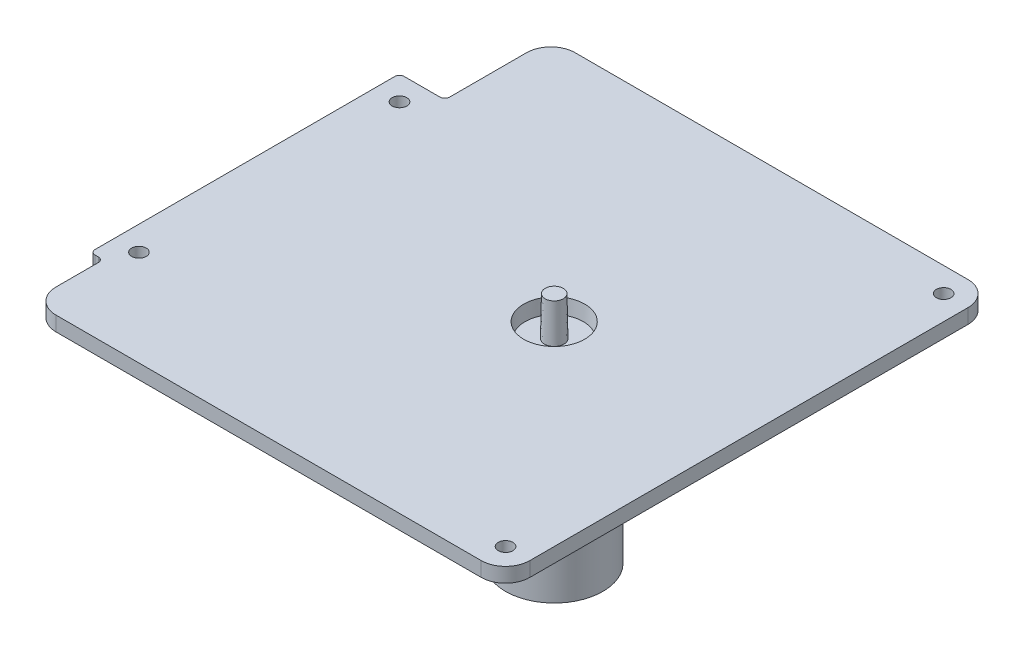
SolidWorks part; units mm, degrees
ref_plane "Front Plane" through (0, 0, 0) normal (0, 0, 1) x (1, 0, 0)
ref_plane "Top Plane" through (0, 0, 0) normal (0, 1, 0) x (1, 0, 0)
ref_plane "Right Plane" through (0, 0, 0) normal (1, 0, 0) x (0, 0, -1)
ref_plane "Plane1" through (0, 23, 0) normal (0, 1, 0) x (1, 0, 0)
sketch "Sketch1" plane through (0, 23, 0) normal (0, 1, 0) x (1, 0, 0)
  line L0 (98.3054, 50) -> (98.3054, 28.2195)
  line L1 (189, 50) -> (98.3054, 50)
  line L2 (189, 50) -> (189, -50)
  line L3 (189, -50) -> (97.6502, -50)
  line L5 (98.3054, 28.2195) -> (89, 28.2195)
  line L6 (89, 28.2195) -> (89, -35.308)
  line L7 (89, -35.308) -> (91.6598, -35.308)
  line L8 (91.6598, -35.308) -> (91.6598, -50)
  line L9 (91.6598, -50) -> (97.6502, -50)
  line L10 (94.8054, 33.2195) -> (98.3054, 33.2195) construction
  line L11 (184, 45) -> (184, 50) construction
  line L12 (93.3054, 31.7195) -> (93.3054, 28.2195) construction
  line L13 (99.4745, -35.308) -> (86.1225, -35.308) construction
  line L14 (88.1598, -40.308) -> (91.6598, -40.308) construction
  line L15 (86.6598, -38.808) -> (86.6598, -35.308) construction
  line L16 (189, 0) -> (190, 0) construction
  line L17 (190, -60) -> (190, 60) construction
  line L18 (105.0183, -40) -> (185.0183, -40) construction
  line L19 (105.0183, -40) -> (105.0183, 40) construction
  line L20 (105.0183, 40) -> (185.0183, 40) construction
  line L21 (185.0183, -40) -> (185.0183, 40) construction
  line L22 (184, 45) -> (189, 45) construction
  line L23 (184, -45) -> (189, -45) construction
  line L24 (184, -45) -> (184, -50) construction
  line L25 (94, 23.2195) -> (94, 28.2195) construction
  line L26 (94, 23.2195) -> (89, 23.2195) construction
  line L27 (94, -30.308) -> (94, -35.308) construction
  line L28 (94, -30.308) -> (89, -30.308) construction
  line L29 (190, -55) -> (190, 55) construction
  circle A0 centre (86.6598, -40.308) radius 1.5 construction
  circle A1 centre (93.3054, 33.2195) radius 1.5 construction
  circle A2 centre (184, 45) radius 1.5 construction
  circle A3 centre (184, 45) radius 1.5 construction
  circle A4 centre (184, -45) radius 1.5 construction
  circle A6 centre (94, 23.2195) radius 1.5 construction
  circle A7 centre (94, -30.308) radius 1.5 construction
  point P32 (185.0183, 0)
  dimension "D1" = 100
  dimension "D2" = 80
  dimension "D3" = 3.5
  dimension "D4" = 5
  dimension "D5" = 1
  dimension "D6" = 100
extrude "Boss-Extrude1" add sketch "Sketch1" along normal blind 3
fillet "Fillet3" radius 5 4 edges at (189, 24.5, -50) (98.3054, 24.5, -50) (91.6598, 24.5, 50) (189, 24.5, 50)
fillet "Fillet2" radius 1 4 edges at (89, 24.5, -28.2195) (98.3054, 24.5, -28.2195) (91.6598, 24.5, 35.308) (89, 24.5, 35.308)
sketch "Sketch2" plane through (0, 23, 0) normal (0, 1, 0) x (1, 0, 0)
  circle A0 centre (184, -45) radius 1.5 construction
  circle A1 centre (184, -45) radius 1.5
  circle A2 centre (94, -30.308) radius 1.5 construction
  circle A3 centre (94, -30.308) radius 1.5
  circle A4 centre (94, 23.2195) radius 1.5 construction
  circle A5 centre (94, 23.2195) radius 1.5
  circle A6 centre (184, 45) radius 1.5 construction
  circle A7 centre (184, 45) radius 1.5
extrude "Cut-Extrude1" cut sketch "Sketch2" along normal up to surface (3 mm away) up to face at (116.9913, 26, 1.7721)
sketch "Sketch5" plane through (0, 23, 0) normal (0, 1, 0) x (1, 0, 0)
  line L0 (189, 50) -> (189, -50) construction
  circle A0 centre (149, 0) radius 10
  circle A1 centre (149, 0) radius 6 construction
  circle A2 centre (149, 0) radius 2 construction
  point P4 (189, 0)
  dimension "D2" = 20
  dimension "D3" = 12
  dimension "D4" = 4
  dimension "D1" = 40
extrude "Boss-Extrude2" add sketch "Sketch5" against normal blind 40
sketch "Sketch3" plane through (0, 23, 0) normal (0, 1, 0) x (1, 0, 0)
  line L0 (189, 50) -> (189, -50) construction
  circle A0 centre (149, 0) radius 6
  circle A1 centre (149, 0) radius 6 construction
  point P6 (189, 0)
extrude "Cut-Extrude3" cut sketch "Sketch3" along normal blind 3 draft 5 draft outward yes
sketch "Sketch6" plane through (0, 23, 0) normal (0, 1, 0) x (1, 0, 0)
  circle A0 centre (149, 0) radius 2
  circle A1 centre (149, 0) radius 2 construction
extrude "Boss-Extrude3" add sketch "Sketch6" along normal blind 8 draft 1
